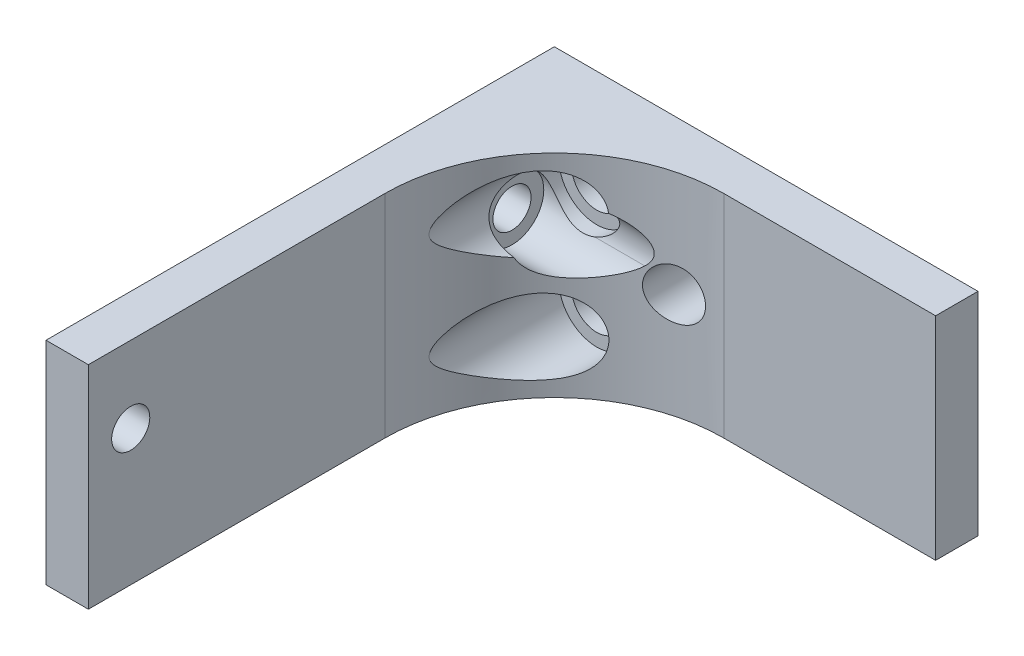
SolidWorks part; units mm, degrees
ref_plane "Alzado" through (0, 0, 0) normal (0, 0, 1) x (1, 0, 0)
ref_plane "Planta" through (0, 0, 0) normal (0, 1, 0) x (1, 0, 0)
ref_plane "Vista lateral" through (0, 0, 0) normal (1, 0, 0) x (0, 0, -1)
sketch "Croquis1" plane through (0, 0, 0) normal (0, 0, 1) x (1, 0, 0)
  line L0 (10, 18.75) -> (10, 6.25) construction
  line L1 (0, 0) -> (50, 0)
  line L2 (0, 0) -> (0, 25)
  line L3 (0, 25) -> (50, 25)
  line L4 (50, 0) -> (50, 25)
  line L6 (0, 25) -> (5, 25)
  line L7 (0, 25) -> (0, 0)
  line L8 (0, 0) -> (5, 0)
  line L9 (5, 25) -> (5, 0)
  circle A0 centre (10, 18.75) radius 2.95
  circle A1 centre (10, 6.25) radius 2.95
  circle A2 centre (20, 12.5) radius 2.95
  point P12 (10, 12.5)
  point P13 (0, 12.5)
  dimension "D3" = 5.9
  dimension "D5" = 10
  dimension "D1" = 50
  dimension "D2" = 25
  dimension "D4" = 12.5
  dimension "D6" = 10
  dimension "D7" = 5
extrude "Saliente-Extruir1" add sketch "Croquis1" along normal blind 5 contours L3 L9 L1 L4 A2 A0 A1 | L9 L3 L2 L1 region at (2.5, 12.5, 0) region at (28.6141, 12.5, 0)
extrude "Saliente-Extruir2" add sketch "Croquis1<3>" along normal blind 60 contours L9 L3 L2 L1 region at (2.5, 12.5, 0)
sketch "Croquis1<3>" plane through (0, 0, 0) normal (0, 0, 1) x (1, 0, 0) same geometry as "Croquis1"
ref_plane "Plano1" through (0, 12.5, 0) normal (0, 1, 0) x (1, 0, 0)
sketch "Croquis2" [suppressed] plane through (0, 12.5, 0) normal (0, 1, 0) x (1, 0, 0)
  line L0 (10, -5) -> (35, -5)
  line L1 (10, -5) -> (50, -5) construction
  line L2 (35, -5) -> (10, -40)
  line L3 (10, -60) -> (10, -5) construction
  line L4 (10, -40) -> (10, -5)
  dimension "D1" = 35
  dimension "D2" = 25
extrude "Saliente-Extruir3" [suppressed] add sketch "Croquis2" along normal blind 2.5 and the other way blind 2.5
sketch "Croquis3" plane through (0, 0, 5) normal (0, 0, 1) x (1, 0, 0)
  circle A0 centre (20, 12.5) radius 2.95 construction
  circle A1 centre (20, 12.5) radius 2.95
extrude "Cortar-Extruir-Lámina2" [suppressed] cut sketch "Croquis3" along normal through all thin thin type mid plane wall 1.5
fillet "Redondeo2" radius 20 1 edges at (5, 12.5, 5)
sketch "Croquis4" plane through (0, 0, 5) normal (0, 0, 1) x (1, 0, 0)
  arc A3 (14.45, 18.75) -> (14.45, 18.75) centre (10, 18.75) ccw
  circle A5 centre (10, 18.75) radius 4.45
  arc A8 (14.45, 6.25) -> (14.45, 6.25) centre (10, 6.25) ccw
  circle A9 centre (10, 6.25) radius 4.45
  dimension "D1" = 1.5
  dimension "D2" = 1.5
extrude "Cortar-Extruir1" cut sketch "Croquis4" along normal through all
sketch "Croquis5" plane through (5, 0, 0) normal (1, 0, 0) x (0, 0, -1)
  line L0 (-12.25, 16) -> (-60, 16) construction
  line L1 (-60, 25) -> (-60, 0) construction
  line L4 (-60, 0) -> (-25, 0)
  line L5 (-60, 0) -> (-25, 0)
  line L6 (-25, 25) -> (-60, 25)
  line L7 (-60, 25) -> (-60, 0)
  line L10 (-25, 25) -> (-60, 25) construction
  line L11 (-60, 25) -> (-60, 0) construction
  line L14 (-25, 0) -> (-25, 25)
  line L15 (-25, 0) -> (-25, 25)
  circle A0 centre (-55, 16) radius 2.25
  circle A1 centre (-10, 16) radius 2.25
  dimension "D5" = 4.5
  dimension "D2" = 9
  dimension "D3" = 5
  dimension "D4" = 45
  dimension "D1" = 0
extrude "Cortar-Extruir2" cut sketch "Croquis5" against normal through all contours A0 | A1
extrude "Cortar-Extruir-Lámina3" cut sketch "Croquis5<3>" along normal through all thin contours A1 body kept at (0, 25, 60) thin type one direction wall 1.5
sketch "Croquis5<3>" plane through (5, 0, 0) normal (1, 0, 0) x (0, 0, -1) same geometry as "Croquis5"
